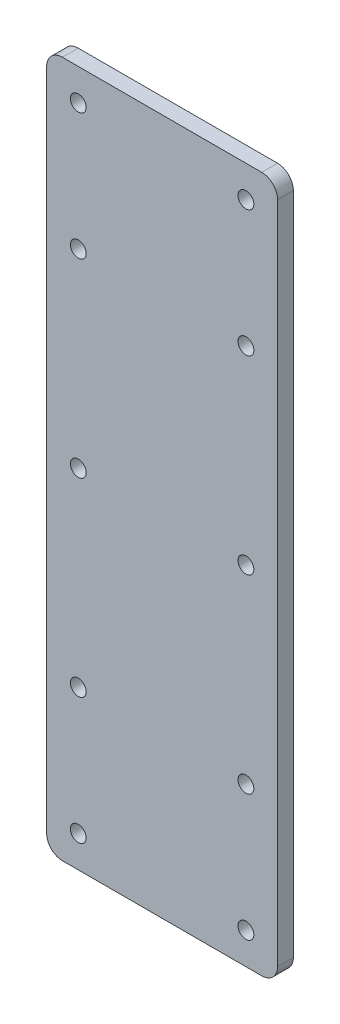
SolidWorks part; units mm, degrees
material "6061 Alloy"
ref_plane "Front Plane" through (0, 0, 0) normal (0, 0, 1) x (1, 0, 0)
ref_plane "Top Plane" through (0, 0, 0) normal (0, 1, 0) x (1, 0, 0)
ref_plane "Right Plane" through (0, 0, 0) normal (1, 0, 0) x (0, 0, -1)
sketch "Sketch2" plane through (0, 0, 0) normal (0, 0, 1) x (1, 0, 0)
  line L0 (36.5, 220) -> (36.5, 0) construction
  line L1 (5, 0) -> (68, 0)
  line L2 (0, 5) -> (0, 215)
  line L3 (5, 220) -> (68, 220)
  line L4 (73, 5) -> (73, 215)
  line L5 (10, 210) -> (63, 210)
  line L6 (10, 210) -> (10, 170)
  line L7 (10, 170) -> (63, 170)
  line L8 (63, 210) -> (63, 170)
  line L9 (0, 110) -> (73, 110) construction
  line L10 (10, 50) -> (63, 50)
  line L11 (10, 50) -> (10, 10)
  line L12 (10, 10) -> (63, 10)
  line L13 (63, 50) -> (63, 10)
  circle A0 centre (10, 210) radius 2.5
  circle A1 centre (63, 210) radius 2.5
  circle A2 centre (63, 170) radius 2.5
  circle A3 centre (10, 170) radius 2.5
  circle A4 centre (63, 50) radius 2.5
  circle A5 centre (10, 50) radius 2.5
  circle A6 centre (10, 10) radius 2.5
  circle A7 centre (63, 10) radius 2.5
  circle A8 centre (10, 110) radius 2.5
  circle A9 centre (63, 110) radius 2.5
  arc A10 (5, 0) -> (0, 5) centre (5, 5) cw
  arc A11 (68, 0) -> (73, 5) centre (68, 5) ccw
  arc A12 (68, 220) -> (73, 215) centre (68, 215) cw
  arc A13 (0, 215) -> (5, 220) centre (5, 215) cw
  point P11 (36.5, 210)
  point P20 (36.5, 10)
  point P34 (0, 0)
  dimension "D5" = 5
  dimension "D8" = 5
  dimension "D1" = 53
  dimension "D2" = 40
  dimension "D3" = 10
  dimension "D4" = 10
  dimension "D6" = 120
  dimension "D7" = 10
extrude "Boss-Extrude1" add sketch "Sketch2" along normal blind 5 contours A13 L2 A10 L1 A11 L4 A12 L3 A9 A8 A7 L12 A6 L11 A5 L10 A4 L13 A3 L6 A0 L5 A1 L8 A2 L7 | A3 L7 A2 L8 A1 L5 A0 L6 | A7 L13 A4 L10 A5 L11 A6 L12 region at (36.5, 110, 0) region at (36.5, 190, 0) region at (36.5, 30, 0)
